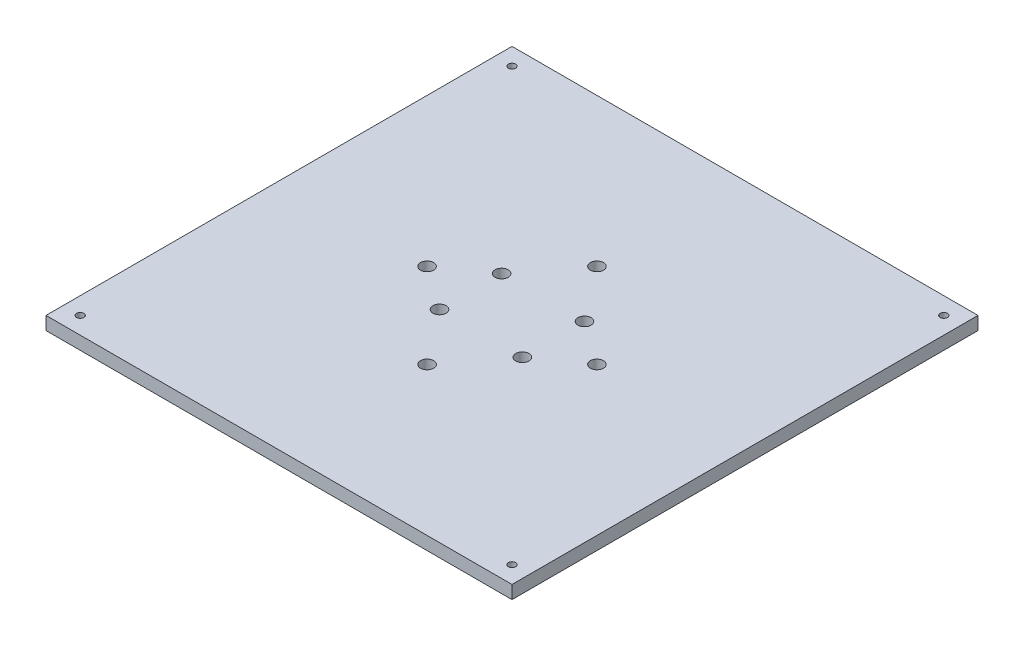
SolidWorks part; units mm, degrees
ref_plane "Front Plane" through (0, 0, 0) normal (0, 0, 1) x (1, 0, 0)
ref_plane "Top Plane" through (0, 0, 0) normal (0, 1, 0) x (1, 0, 0)
ref_plane "Right Plane" through (0, 0, 0) normal (1, 0, 0) x (0, 0, -1)
sketch "Sketch1" plane through (0, 0, 0) normal (0, 1, 0) x (1, 0, 0)
  line L1 (0, 0) -> (225, 0)
  line L2 (0, 0) -> (0, 225)
  line L3 (0, 225) -> (225, 225)
  line L4 (225, 0) -> (225, 225)
  line L5 (0, 0) -> (225, 225) construction
  line L6 (0, 225) -> (225, 0) construction
  point P4 (112.5, 112.5)
  dimension "D1" = 225
  dimension "D2" = 225
extrude "Boss-Extrude1" add sketch "Sketch1" along normal blind 6.35
sketch "Sketch2" plane through (0, 6.35, 0) normal (0, 1, 0) x (1, 0, 0)
  line L0 (222.5, 222.5) -> (222.5, 225) construction
  line L1 (2.5, 2.5) -> (222.5, 2.5) construction
  line L2 (2.5, 2.5) -> (2.5, 222.5) construction
  line L3 (2.5, 222.5) -> (222.5, 222.5) construction
  line L4 (222.5, 2.5) -> (222.5, 222.5) construction
  line L5 (112.5, 222.5) -> (112.5, 2.5) construction
  line L6 (2.5, 112.5) -> (222.5, 112.5) construction
  line L7 (225, 225) -> (0, 225) construction
  line L8 (222.5, 222.5) -> (225, 222.5) construction
  line L9 (225, 0) -> (225, 225) construction
  line L10 (2.5, 2.5) -> (0, 2.5) construction
  line L11 (0, 225) -> (0, 0) construction
  line L12 (2.5, 2.5) -> (2.5, 0) construction
  line L13 (0, 0) -> (225, 0) construction
  circle A0 centre (216.74, 216.74) radius 1.75
  circle A1 centre (8.26, 216.74) radius 1.75
  circle A2 centre (216.74, 8.26) radius 1.75
  circle A3 centre (8.26, 8.26) radius 1.75
  dimension "D2" = 5.76
  dimension "D4" = 3.5
  dimension "D1" = 220
  dimension "D3" = 5.76
extrude "Cut-Extrude1" cut sketch "Sketch2" against normal through all
sketch "Sketch3" plane through (0, 6.35, 0) normal (0, 1, 0) x (1, 0, 0)
  line L0 (112.5, 0) -> (112.5, 71.4904) construction
  line L3 (0, 0) -> (225, 0) construction
  line L6 (225, 112.5) -> (153.5096, 112.5) construction
  line L7 (153.5096, 71.4904) -> (71.4904, 71.4904)
  line L8 (153.5096, 71.4904) -> (153.5096, 153.5096)
  line L9 (153.5096, 153.5096) -> (71.4904, 153.5096)
  line L10 (71.4904, 71.4904) -> (71.4904, 153.5096)
  line L11 (225, 0) -> (225, 225) construction
  line L12 (0, 112.5) -> (71.4904, 112.5) construction
  line L13 (0, 225) -> (0, 0) construction
  line L14 (112.5, 225) -> (112.5, 153.5096) construction
  line L15 (225, 225) -> (0, 225) construction
  line L16 (112.5, 71.4904) -> (112.5, 153.5096) construction
  line L17 (153.5096, 112.5) -> (71.4904, 112.5) construction
  circle A0 centre (112.5, 71.4904) radius 3.175
  circle A1 centre (71.4904, 112.5) radius 3.175
  circle A2 centre (112.5, 153.5096) radius 3.175
  circle A3 centre (153.5096, 112.5) radius 3.175
  circle A4 centre (92.5, 97.5) radius 3.175
  circle A5 centre (92.5, 127.5) radius 3.175
  circle A6 centre (132.5, 127.5) radius 3.175
  circle A7 centre (132.5, 97.5) radius 3.175
  point P20 (112.5, 153.5096)
  point P22 (153.5096, 112.5)
  point P34 (0, 0)
  point P35 (0, 0)
  point P36 (0, 0)
  point P37 (0, 0)
  point P38 (0, 0)
  point P41 (131.6515, 134.7761)
  dimension "D2" = 6.35
  dimension "D1" = 82.0192
  dimension "D3" = 20
  dimension "D4" = 15
  dimension "D5" = 20
  dimension "D6" = 15
extrude "Cut-Extrude2" cut sketch "Sketch3" against normal through all contours L8 A3 | L8 A3 | A6 | A7 | A4 | A5 | L10 A1 | L10 A1 | L9 A2 | L9 A2 | L7 A0 | L7 A0 region at (112.5, 6.35, -70.1429) region at (112.5, 6.35, -72.8379) region at (152.1621, 6.35, -112.5) region at (154.8571, 6.35, -112.5) region at (70.1429, 6.35, -112.5) region at (72.8379, 6.35, -112.5) region at (112.5, 6.35, -152.1621) region at (112.5, 6.35, -154.8571) region at (92.5, 6.35, -97.5) region at (92.5, 6.35, -127.5) region at (132.5, 6.35, -127.5) region at (132.5, 6.35, -97.5)
